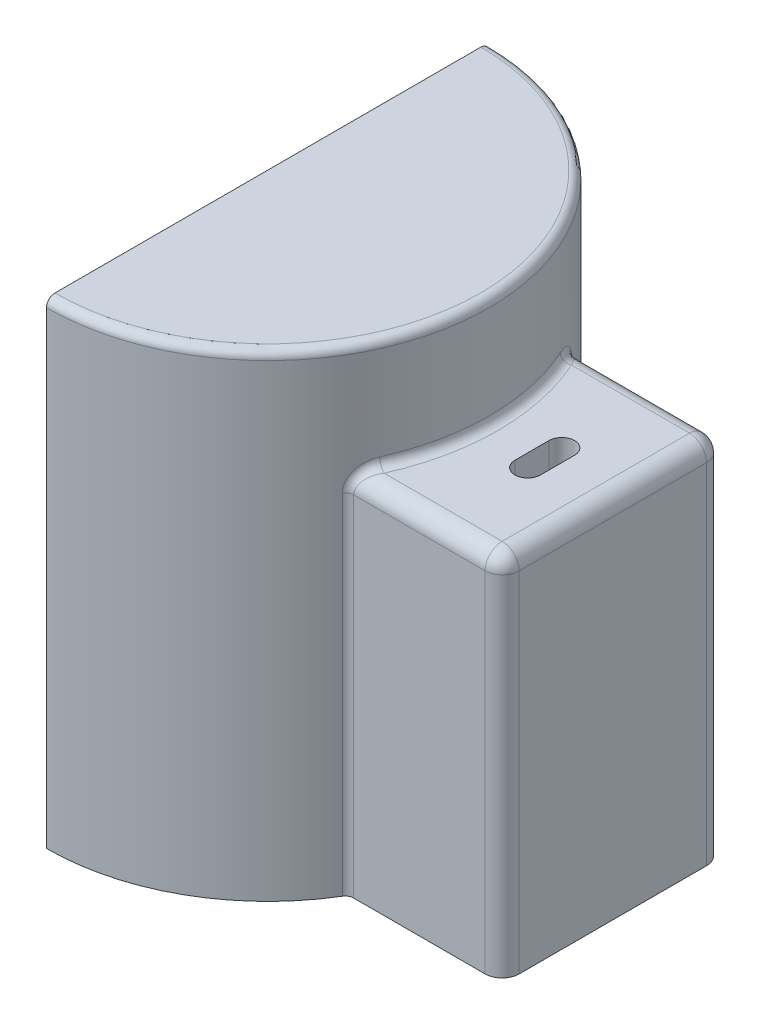
SolidWorks part; units mm, degrees
ref_plane "Спереди" through (0, 0, 0) normal (0, 0, 1) x (1, 0, 0)
ref_plane "Сверху" through (0, 0, 0) normal (0, 1, 0) x (1, 0, 0)
ref_plane "Справа" through (0, 0, 0) normal (1, 0, 0) x (0, 0, -1)
sketch "Эскиз1" plane through (0, 0, 0) normal (0, 1, 0) x (1, 0, 0)
  line L0 (0, 0) -> (0, 18805.5356) construction
  line L1 (0, 0) -> (-18805.5356, 0) construction
  line L2 (0, 26) -> (0, 23)
  line L3 (0, -23) -> (0, -26)
  line L4 (22.5167, 13) -> (40.5167, 13)
  line L5 (40.5167, 13) -> (40.5167, -13)
  line L6 (40.5167, -13) -> (22.5167, -13)
  line L7 (20.7123, -10) -> (37.5167, -10)
  line L8 (37.5167, -10) -> (37.5167, 10)
  line L9 (37.5167, 10) -> (20.7123, 10)
  arc A0 (0, -26) -> (24, -10) centre (0, 0) ccw
  arc A1 (0, -23) -> (20.7123, -10) centre (0, 0) ccw
  arc A2 (20.7123, 10) -> (0, 23) centre (0, 0) ccw
  arc A3 (24, 10) -> (0, 26) centre (0, 0) ccw
  dimension "D1" = 46
  dimension "D2" = 52
  dimension "D3" = 26
  dimension "D4" = 18
  dimension "D5" = 20
  dimension "D6" = 3
extrude "Бобышка-Вытянуть1" add sketch "Эскиз1" along normal blind 43 contours A1 L3 A0 L7 | A3 L9 L8 L7 A0 L6 L5 L4 | L9 A3 L2 A2 region at (12.632, 0, -19.4701) region at (31.5167, 0, -12.6838) region at (12.632, 0, 19.4701)
sketch "Эскиз2" plane through (0, 43, 0) normal (0, 1, 0) x (1, 0, 0)
  line L0 (0, 26) -> (0, 23)
  line L1 (0, -26) -> (0, -23)
  arc A0 (0, -26) -> (0, 26) centre (0, 0) ccw
  arc A1 (0, -23) -> (0, 23) centre (0, 0) ccw
extrude "Бобышка-Вытянуть2" add sketch "Эскиз2" along normal blind 13
sketch "Эскиз3" plane through (0, 56, 0) normal (0, 1, 0) x (1, 0, 0)
  line L0 (0, 26) -> (0, -26)
  arc A0 (0, -26) -> (0, 26) centre (0, 0) ccw
extrude "Бобышка-Вытянуть3" add sketch "Эскиз3" against normal blind 3
fillet "Скругление1" radius 1 5 edges at (22.5167, 21.5, 13) (22.5167, 21.5, -13) (37.5167, 21.5, -10) (37.5167, 21.5, 10) (26, 56, 0)
fillet "Скругление2" radius 2 2 edges at (40.5167, 21.5, -13) (40.5167, 21.5, 13)
sketch "Эскиз5" plane through (0, 43, 0) normal (0, 1, 0) x (1, 0, 0)
  line L3 (20.7123, 10) -> (37.5167, 10)
  line L4 (37.5167, 10) -> (37.5167, -10)
  line L5 (37.5167, -10) -> (20.7123, -10)
  line L6 (37.5167, -9) -> (37.5167, 9) construction
  arc A2 (20.7123, -10) -> (20.7123, 10) centre (0, 0) ccw
  point P3 (20.8791, 9.6469)
extrude "Бобышка-Вытянуть4" add sketch "Эскиз5" against normal blind 3
fillet "Скругление3" radius 1 5 edges at (28.6145, 40, 10) (37.2238, 40, 9.7071) (28.6145, 40, -10) (37.2238, 40, -9.7071) (37.5167, 40, 0)
fillet "Скругление4" radius 2 7 edges at (22.5961, 43, -13.1286) (30.8017, 43, -13) (39.9309, 43, -12.4142) (22.5961, 43, 13.1286) (30.8017, 43, 13) (39.9309, 43, 12.4142) (40.5167, 43, 0)
fillet "Скругление5" radius 1 3 edges at (22.7135, 42.197, 12.653) (22.7135, 42.197, -12.653) (26, 43, 0)
sketch "Эскиз6" plane through (0, 43, 0) normal (0, 1, 0) x (1, 0, 0)
  line L0 (32.5167, -2) -> (32.5167, 2) construction
  line L1 (31.0167, -2) -> (31.0167, 2)
  line L2 (34.0167, -2) -> (34.0167, 2)
  line L3 (38.5167, -11) -> (38.5167, 11) construction
  arc A0 (31.0167, -2) -> (34.0167, -2) centre (32.5167, -2) ccw
  arc A1 (34.0167, 2) -> (31.0167, 2) centre (32.5167, 2) ccw
  point P2 (32.5167, 0)
  point P7 (0, 0)
  point P10 (38.5167, 0)
  dimension "D1" = 1.5
  dimension "D2" = 4
  dimension "D3" = 6
extrude "Вырез-Вытянуть1" cut sketch "Эскиз6" against normal through all
